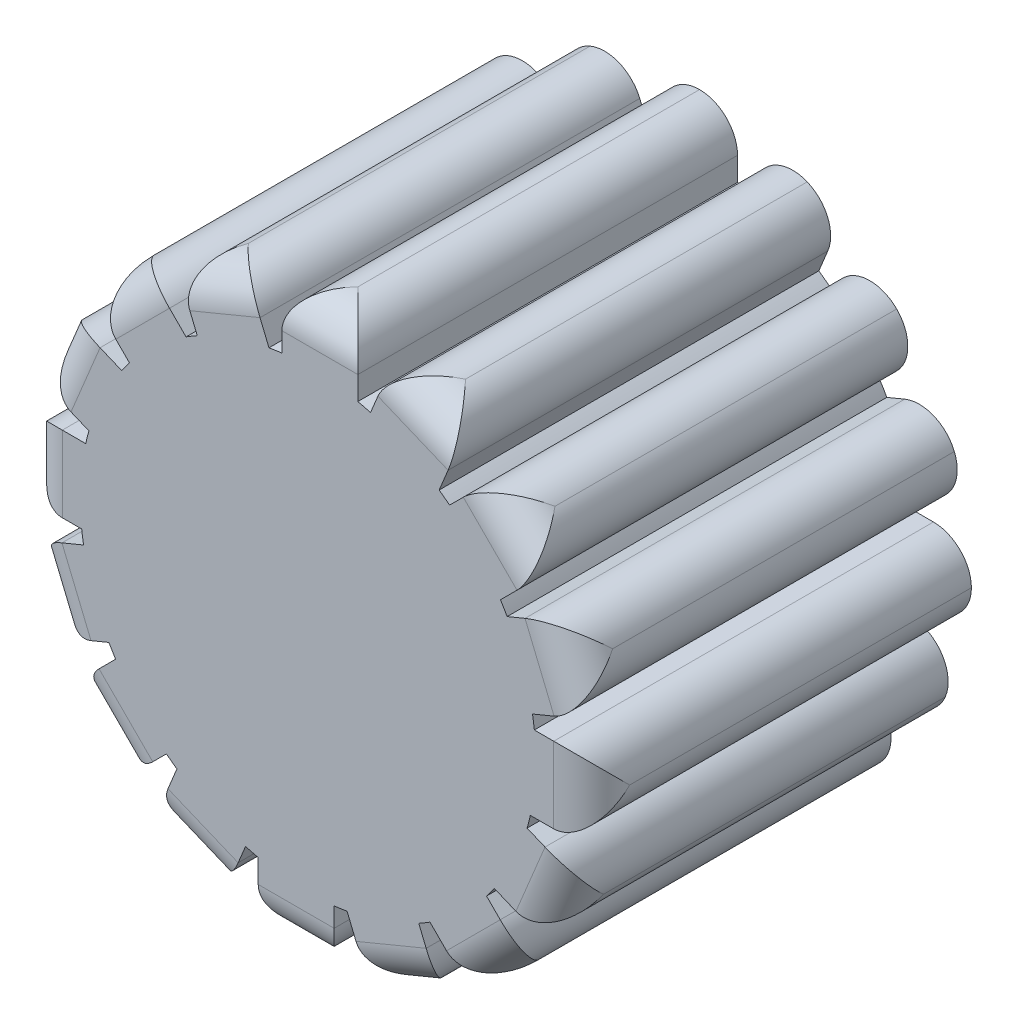
SolidWorks part; units mm, degrees
ref_plane "Front Plane" through (0, 0, 0) normal (0, 0, 1) x (1, 0, 0)
ref_plane "Top Plane" through (0, 0, 0) normal (0, 1, 0) x (1, 0, 0)
ref_plane "Right Plane" through (0, 0, 0) normal (1, 0, 0) x (0, 0, -1)
sketch "Sketch1" plane through (0, 0, 0) normal (0, 0, 1) x (1, 0, 0)
  circle A0 centre (-68.3905, -10.4636) radius 6
  point P3 (-68.3905, -10.4636)
  point P4 (0, 0)
  point P5 (0, 0)
  dimension "D1" = 12
extrude "Boss-Extrude3" add sketch "Sketch1" along normal blind 10
sketch "Sketch3" plane through (0, 0, 0) normal (0, 0, -1) x (-1, 0, 0)
  line L0 (70.9885, -11.9636) -> (65.7924, -11.9636)
  arc A0 (70.9885, -11.9636) -> (65.7924, -11.9636) centre (68.3905, -10.4636) ccw
  dimension "D1" = 6
  dimension "D2" = 4.5
extrude "Cut-Extrude1" cut sketch "Sketch3" against normal blind 8
sketch "Sketch4" plane through (0, 0, 0) normal (0, 0, -1) x (-1, 0, 0)
  circle A0 centre (68.3905, -10.4636) radius 4.5
  dimension "D1" = 9
extrude "Cut-Extrude2" cut sketch "Sketch4" against normal blind 3
sketch "Sketch6" plane through (0, 0, 10) normal (0, 0, 1) x (1, 0, 0)
  line L1 (-69.7027, -15.9349) -> (-67.7027, -15.9349)
  line L2 (-69.7027, -15.9349) -> (-69.7027, -17.9349)
  line L3 (-69.7027, -17.9349) -> (-67.7027, -17.9349)
  line L4 (-67.7027, -15.9349) -> (-67.7027, -17.9349)
  line L5 (-69.7027, -15.9349) -> (-67.7027, -17.9349) construction
  line L6 (-69.7027, -17.9349) -> (-67.7027, -15.9349) construction
  point P0 (-68.7027, -16.9349)
  dimension "D1" = 2
  dimension "D2" = 2
extrude "Boss-Extrude5" add sketch "Sketch6" against normal blind 10
fillet "Fillet8" radius 1 3 edges at (-68.7027, -17.9349, 10) (-67.7027, -17.9349, 5) (-69.7027, -17.9349, 5)
pattern_circular "CirPattern11" count 16 over 360 about axis through (-68.3905, -10.4636, 10) along (0, 0, -1) of "Boss-Extrude5", "Fillet8"
